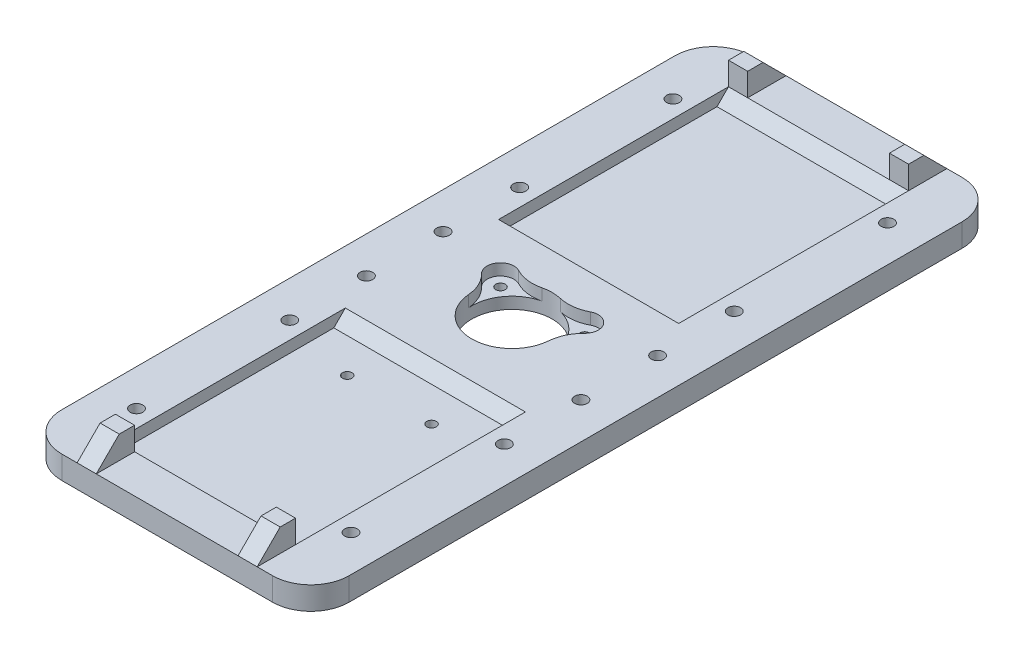
SolidWorks part; units mm, degrees
ref_plane "Front Plane" through (0, 0, 0) normal (0, 0, 1) x (1, 0, 0)
ref_plane "Top Plane" through (0, 0, 0) normal (0, 1, 0) x (1, 0, 0)
ref_plane "Right Plane" through (0, 0, 0) normal (1, 0, 0) x (0, 0, -1)
sketch "Sketch1" plane through (0, 0, 0) normal (0, 1, 0) x (1, 0, 0)
  line L1 (-37.5, 90) -> (37.5, 90)
  line L2 (-37.5, 90) -> (-37.5, -90)
  line L3 (-37.5, -90) -> (37.5, -90)
  line L4 (37.5, 90) -> (37.5, -90)
  dimension "D1" = 180
  dimension "D2" = 75
  dimension "D3" = 90
  dimension "D4" = 37.5
extrude "Boss-Extrude1" add sketch "Sketch1" along normal blind 6
fillet "Fillet1" radius 10 4 edges at (-37.5, 3, 90) (-37.5, 3, -90) (37.5, 3, -90) (37.5, 3, 90)
sketch "Sketch2" plane through (0, 6, 0) normal (0, 1, 0) x (1, 0, 0)
  line L0 (-27.5, -90) -> (27.5, -90) construction
  line L1 (-37.5, 80) -> (-37.5, -80) construction
  line L2 (37.5, -80) -> (37.5, 80) construction
  line L3 (27.5, 90) -> (-27.5, 90) construction
  line L4 (-37.5, 80) -> (-37.5, -80) construction
  circle A0 centre (0, 0) radius 10.5
  circle A1 centre (-11, 8) radius 1.25
  circle A2 centre (11, 8) radius 1.25
  circle A3 centre (-11, -32) radius 1.25
  circle A4 centre (11, -32) radius 1.25
  circle A5 centre (-28, -70) radius 1.65
  circle A6 centre (28, -70) radius 1.65
  circle A7 centre (-28, 70) radius 1.65
  circle A8 centre (28, 70) radius 1.65
  circle A9 centre (-28, 10) radius 1.65
  circle A10 centre (-28, -10) radius 1.65
  circle A11 centre (28, 10) radius 1.65
  circle A12 centre (28, -10) radius 1.65
  circle A13 centre (-28, 30) radius 1.65
  circle A14 centre (28, 30) radius 1.65
  circle A15 centre (28, -30) radius 1.65
  circle A16 centre (-28, -30) radius 1.65
  dimension "D1" = 21
  dimension "D5" = 2.5
  dimension "D6" = 2.5
  dimension "D11" = 2.5
  dimension "D12" = 2.5
  dimension "D14" = 3.3
  dimension "D15" = 3.3
  dimension "D20" = 3.3
  dimension "D21" = 3.3
  dimension "D34" = 3.3
  dimension "D35" = 3.3
  dimension "D36" = 3.3
  dimension "D37" = 3.3
  dimension "D38" = 3.3
  dimension "D43" = 3.3
  dimension "D45" = 3.3
  dimension "D47" = 3.3
  dimension "D2" = 8
  dimension "D3" = 22
  dimension "D4" = 11
  dimension "D7" = 8
  dimension "D8" = 40
  dimension "D9" = 22
  dimension "D10" = 11
  dimension "D13" = 40
  dimension "D16" = 20
  dimension "D17" = 20
  dimension "D18" = 9.5
  dimension "D19" = 9.5
  dimension "D22" = 20
  dimension "D23" = 20
  dimension "D24" = 9.5
  dimension "D25" = 9.5
  dimension "D26" = 20
  dimension "D27" = 10
  dimension "D28" = 10
  dimension "D29" = 20
  dimension "D30" = 9.5
  dimension "D31" = 9.5
  dimension "D32" = 9.5
  dimension "D33" = 9.5
  dimension "D39" = 20
  dimension "D40" = 9.5
  dimension "D41" = 9.5
  dimension "D42" = 20
  dimension "D44" = 20
  dimension "D46" = 9.5
  dimension "D48" = 9.5
  dimension "D49" = 20
extrude "Cut-Extrude1" cut sketch "Sketch2" against normal blind 10
sketch "Sketch4" plane through (0, 0, 0) normal (0, -1, 0) x (1, 0, 0)
  line L1 (-28, 6.7668) -> (-25.2, 8.3834)
  line L2 (-25.2, 8.3834) -> (-25.2, 11.6166)
  line L3 (-25.2, 11.6166) -> (-28, 13.2332)
  line L4 (-28, 13.2332) -> (-30.8, 11.6166)
  line L5 (-30.8, 11.6166) -> (-30.8, 8.3834)
  line L6 (-30.8, 8.3834) -> (-28, 6.7668)
  line L7 (-27.9206, -13.2322) -> (-25.1611, -11.5473)
  line L8 (-25.1611, -11.5473) -> (-25.2406, -8.3151)
  line L9 (-25.2406, -8.3151) -> (-28.0794, -6.7678)
  line L10 (-28.0794, -6.7678) -> (-30.8389, -8.4527)
  line L11 (-30.8389, -8.4527) -> (-30.7594, -11.6849)
  line L12 (-30.7594, -11.6849) -> (-27.9206, -13.2322)
  line L13 (28, -13.2332) -> (30.8, -11.6166)
  line L14 (30.8, -11.6166) -> (30.8, -8.3834)
  line L15 (30.8, -8.3834) -> (28, -6.7668)
  line L16 (28, -6.7668) -> (25.2, -8.3834)
  line L17 (25.2, -8.3834) -> (25.2, -11.6166)
  line L18 (25.2, -11.6166) -> (28, -13.2332)
  line L19 (28, 6.7668) -> (30.8, 8.3834)
  line L20 (30.8, 8.3834) -> (30.8, 11.6166)
  line L21 (30.8, 11.6166) -> (28, 13.2332)
  line L22 (28, 13.2332) -> (25.2, 11.6166)
  line L23 (25.2, 11.6166) -> (25.2, 8.3834)
  line L24 (25.2, 8.3834) -> (28, 6.7668)
  line L25 (28, 66.7668) -> (30.8, 68.3834)
  line L26 (30.8, 68.3834) -> (30.8, 71.6166)
  line L27 (30.8, 71.6166) -> (28, 73.2332)
  line L28 (28, 73.2332) -> (25.2, 71.6166)
  line L29 (25.2, 71.6166) -> (25.2, 68.3834)
  line L30 (25.2, 68.3834) -> (28, 66.7668)
  line L31 (-28, 66.7668) -> (-25.2, 68.3834)
  line L32 (-25.2, 68.3834) -> (-25.2, 71.6166)
  line L33 (-25.2, 71.6166) -> (-28, 73.2332)
  line L34 (-28, 73.2332) -> (-30.8, 71.6166)
  line L35 (-30.8, 71.6166) -> (-30.8, 68.3834)
  line L36 (-30.8, 68.3834) -> (-28, 66.7668)
  line L37 (28, -73.2332) -> (30.8, -71.6166)
  line L38 (30.8, -71.6166) -> (30.8, -68.3834)
  line L39 (30.8, -68.3834) -> (28, -66.7668)
  line L40 (28, -66.7668) -> (25.2, -68.3834)
  line L41 (25.2, -68.3834) -> (25.2, -71.6166)
  line L42 (25.2, -71.6166) -> (28, -73.2332)
  line L43 (-28, -73.2332) -> (-25.2, -71.6166)
  line L44 (-25.2, -71.6166) -> (-25.2, -68.3834)
  line L45 (-25.2, -68.3834) -> (-28, -66.7668)
  line L46 (-28, -66.7668) -> (-30.8, -68.3834)
  line L47 (-30.8, -68.3834) -> (-30.8, -71.6166)
  line L48 (-30.8, -71.6166) -> (-28, -73.2332)
  circle A0 centre (-28, 10) radius 2.8 construction
  circle A1 centre (-28, -10) radius 2.8 construction
  circle A2 centre (28, -10) radius 2.8 construction
  circle A3 centre (28, 10) radius 2.8 construction
  circle A4 centre (28, 70) radius 2.8 construction
  circle A5 centre (-28, 70) radius 2.8 construction
  circle A6 centre (28, -70) radius 2.8 construction
  circle A7 centre (-28, -70) radius 2.8 construction
  point P64 (-25.2008, -9.9312)
  point P73 (30.8, 10)
  dimension "D1" = 5.6
  dimension "D2" = 5.6
  dimension "D3" = 5.6
  dimension "D4" = 5.6
  dimension "D5" = 5.6
  dimension "D6" = 5.6
  dimension "D7" = 5.6
  dimension "D8" = 5.6
extrude "Cut-Extrude2" cut sketch "Sketch4" against normal blind 3
sketch "Sketch5" plane through (0, 6, 0) normal (0, 1, 0) x (1, 0, 0)
  line L1 (-23.5, 80) -> (23.5, 80)
  line L2 (-23.5, 80) -> (-23.5, 20)
  line L3 (-23.5, 20) -> (23.5, 20)
  line L4 (23.5, 80) -> (23.5, 20)
  line L5 (-23.5, -20) -> (23.5, -20)
  line L6 (-23.5, -20) -> (-23.5, -80)
  line L7 (-23.5, -80) -> (23.5, -80)
  line L8 (23.5, -20) -> (23.5, -80)
  circle A0 centre (-11, 8) radius 3.5
  circle A1 centre (11, 8) radius 3.5
  dimension "D9" = 7
  dimension "D10" = 7
  dimension "D1" = 20
  dimension "D2" = 47
  dimension "D3" = 23.5
  dimension "D4" = 60
  dimension "D5" = 20
  dimension "D6" = 47
  dimension "D7" = 23.5
  dimension "D8" = 60
extrude "Cut-Extrude3" cut sketch "Sketch5" against normal blind 3
fillet "Fillet2" radius 10 4 edges at (-9.2498, 4.5, -4.969) (-7.5772, 4.5, -7.2688) (9.2498, 4.5, -4.969) (7.5772, 4.5, -7.2688)
chamfer "Chamfer1" distance 3 angle 45 4 edges at (0, 3, 80) (0, 3, -80) (0, 3, -20) (0, 3, 20)
sketch "Sketch6" plane through (0, 6, 0) normal (0, 1, 0) x (1, 0, 0)
  line L0 (27.5, 90) -> (-27.5, 90) construction
  line L1 (-18.5, 90) -> (-23.5, 90)
  line L2 (-18.5, 90) -> (-18.5, 80)
  line L3 (-18.5, 80) -> (-23.5, 80)
  line L4 (-23.5, 90) -> (-23.5, 80)
  line L5 (-27.5, -90) -> (27.5, -90) construction
  line L6 (18.5, -90) -> (23.5, -90)
  line L7 (18.5, -90) -> (18.5, -80)
  line L8 (18.5, -80) -> (23.5, -80)
  line L9 (23.5, -90) -> (23.5, -80)
  line L10 (37.5, -80) -> (37.5, 80) construction
  line L11 (-37.5, 80) -> (-37.5, -80) construction
  line L13 (23.5, 90) -> (18.5, 90)
  line L14 (23.5, 90) -> (23.5, 80)
  line L15 (23.5, 80) -> (18.5, 80)
  line L16 (18.5, 90) -> (18.5, 80)
  line L17 (-23.5, -90) -> (-18.5, -90)
  line L18 (-23.5, -90) -> (-23.5, -80)
  line L19 (-23.5, -80) -> (-18.5, -80)
  line L20 (-18.5, -90) -> (-18.5, -80)
  point P12 (-18.5, 85)
  dimension "D1" = 5
  dimension "D2" = 10
  dimension "D3" = 5
  dimension "D4" = 10
  dimension "D5" = 14
  dimension "D6" = 14
  dimension "D7" = 10
  dimension "D8" = 14
  dimension "D9" = 5
  dimension "D10" = 14
  dimension "D11" = 10
  dimension "D12" = 5
extrude "Boss-Extrude2" add sketch "Sketch6" along normal blind 6
chamfer "Chamfer2" distance 6 angle 45 4 edges at (21, 12, 90) (-21, 12, -90) (21, 12, -90) (-21, 12, 90)
